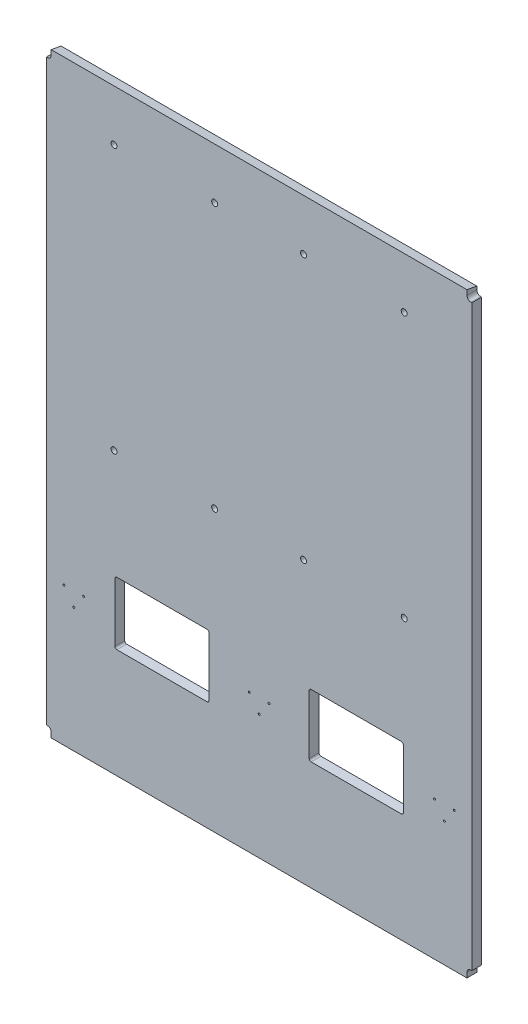
SolidWorks part; units mm, degrees
ref_plane "Front Plane" through (0, 0, 0) normal (0, 0, 1) x (1, 0, 0)
ref_plane "Top Plane" through (0, 0, 0) normal (0, 1, 0) x (1, 0, 0)
ref_plane "Right Plane" through (0, 0, 0) normal (1, 0, 0) x (0, 0, -1)
sketch "Sketch1" plane through (0, 0, 0) normal (0, 0, 1) x (1, 0, 0)
  line L1 (336.55, 482.6) -> (-336.55, 482.6)
  line L2 (336.55, 482.6) -> (336.55, -482.6)
  line L3 (336.55, -482.6) -> (-336.55, -482.6)
  line L4 (-336.55, 482.6) -> (-336.55, -482.6)
  line L5 (336.55, 482.6) -> (-336.55, -482.6) construction
  line L6 (336.55, -482.6) -> (-336.55, 482.6) construction
  point P0 (0, 0)
  dimension "D1" = 673.1
  dimension "D2" = 965.2
extrude "Boss-Extrude1" add sketch "Sketch1" along normal mid plane 15.875
sketch "Sketch2" plane through (0, 0, 7.9375) normal (0, 0, 1) x (1, 0, 0)
  line L0 (0, 0) -> (0, -482.6) construction
  line L1 (-336.55, -482.6) -> (336.55, -482.6) construction
  line L2 (-336.55, 482.6) -> (-336.55, -482.6) construction
  line L3 (-230.3281, -204.0862) -> (-84.2781, -204.0862)
  line L4 (-233.5031, -207.2612) -> (-233.5031, -302.5112)
  line L5 (-230.3281, -305.6862) -> (-84.2781, -305.6862)
  line L6 (-81.1031, -207.2612) -> (-81.1031, -302.5112)
  line L7 (-336.55, -482.6) -> (336.55, -482.6) construction
  line L8 (81.1031, -207.2612) -> (81.1031, -302.5112)
  line L9 (230.3281, -305.6862) -> (84.2781, -305.6862)
  line L10 (233.5031, -207.2612) -> (233.5031, -302.5112)
  line L11 (230.3281, -204.0862) -> (84.2781, -204.0862)
  arc A1 (-84.2781, -204.0862) -> (-81.1031, -207.2612) centre (-84.2781, -207.2612) cw
  arc A2 (-84.2781, -305.6862) -> (-81.1031, -302.5112) centre (-84.2781, -302.5112) ccw
  arc A3 (-233.5031, -302.5112) -> (-230.3281, -305.6862) centre (-230.3281, -302.5112) ccw
  arc A4 (-230.3281, -204.0862) -> (-233.5031, -207.2612) centre (-230.3281, -207.2612) ccw
  arc A5 (230.3281, -204.0862) -> (233.5031, -207.2612) centre (230.3281, -207.2612) cw
  arc A6 (233.5031, -302.5112) -> (230.3281, -305.6862) centre (230.3281, -302.5112) cw
  arc A7 (84.2781, -305.6862) -> (81.1031, -302.5112) centre (84.2781, -302.5112) cw
  arc A8 (84.2781, -204.0862) -> (81.1031, -207.2612) centre (84.2781, -207.2612) ccw
  point P6 (-81.1031, -204.0862)
  point P11 (-233.5031, -305.6862)
  point P14 (-233.5031, -204.0862)
  dimension "D1" = 101.6
  dimension "D3" = 3.175
  dimension "D2" = 152.4
  dimension "D4" = 103.0469
  dimension "D5" = 176.9138
extrude "Cut-Extrude1" cut sketch "Sketch2" against normal through all both and the other way through all
sketch "Sketch3" plane through (336.55, 0, 0) normal (1, 0, 0) x (0, 0, -1)
  line L0 (-7.9375, 482.6) -> (7.9375, 479.8008)
  line L1 (7.9375, -482.6) -> (7.9375, 482.6) construction
  line L2 (7.9375, 479.8008) -> (7.9375, 482.6)
  line L3 (7.9375, 482.6) -> (-7.9375, 482.6)
  dimension "D1" = 10
extrude "Cut-Extrude2" cut sketch "Sketch3" against normal through all
sketch "Sketch4" plane through (0, 0, 7.9375) normal (0, 0, 1) x (1, 0, 0)
  line L0 (-336.55, 482.6) -> (-336.55, -482.6) construction
  line L1 (-336.55, 468.3125) -> (-344.4875, 468.3125)
  line L2 (-336.55, 468.3125) -> (-336.55, -468.3125)
  line L3 (-336.55, -468.3125) -> (-344.4875, -468.3125)
  line L4 (-344.4875, 468.3125) -> (-344.4875, -468.3125)
  line L5 (336.55, -482.6) -> (336.55, 482.6) construction
  line L6 (336.55, 468.3125) -> (344.4875, 468.3125)
  line L7 (336.55, 468.3125) -> (336.55, -468.3125)
  line L8 (336.55, -468.3125) -> (344.4875, -468.3125)
  line L9 (344.4875, 468.3125) -> (344.4875, -468.3125)
  line L10 (0, 0) -> (0, 87.9986) construction
  line L12 (0, 0) -> (-174.9175, 0) construction
  line L13 (-336.55, -482.6) -> (336.55, -482.6) construction
  dimension "D1" = 14.2875
  dimension "D2" = 7.9375
  dimension "D3" = 688.975
extrude "Boss-Extrude2" add sketch "Sketch4" against normal up to surface (15.875 mm away) up to face at (0, -1.3996, -7.9375)
fillet "Fillet1" radius 6.35 4 edges at (336.55, -468.3125, 0) (-336.55, -468.3125, 0) (-336.55, 468.3125, 0) (336.55, 468.3125, 0)
sketch "Sketch5" plane through (0, 0, 7.9375) normal (0, 0, 1) x (1, 0, 0)
  line L0 (-301.5961, -297.8717) -> (-145.6989, -297.8717) construction
  line L1 (-300, -280.8717) -> (-300, -246.7738) construction
  line L2 (0, 0) -> (0, -280.8717) construction
  line L3 (-300, -309.3289) -> (-300, -255.3083) construction
  line L4 (-336.55, -482.6) -> (336.55, -482.6) construction
  circle A0 centre (-316, -257.8717) radius 1.5875
  circle A1 centre (-284, -257.8717) radius 1.5875
  circle A2 centre (-300, -280.8717) radius 1.5875
  circle A6 centre (-16, -257.8717) radius 1.5875
  circle A7 centre (16, -257.8717) radius 1.5875
  circle A8 centre (0, -280.8717) radius 1.5875
  circle A9 centre (284, -257.8717) radius 1.5875
  circle A10 centre (300, -280.8717) radius 1.5875
  circle A11 centre (316, -257.8717) radius 1.5875
  dimension "D1" = 3.175
  dimension "D2" = 17
  dimension "D3" = 23
  dimension "D4" = 32
  dimension "D5" = 32
  dimension "D6" = 201.7283
  dimension "D7" = 300
extrude "Cut-Extrude3" cut sketch "Sketch5" against normal blind 8
sketch "Sketch6" plane through (0, 0, -7.9375) normal (0, 0, -1) x (-1, 0, 0)
  line L0 (0, 0) -> (0, 482.6) construction
  circle A0 centre (-234.95, 400.05) radius 4.826
  circle A1 centre (-71.9667, 400.05) radius 4.826
  circle A2 centre (71.9667, 400.05) radius 4.826
  circle A3 centre (234.95, 400.05) radius 4.826
  circle A4 centre (-234.95, -28.575) radius 4.826
  circle A5 centre (-71.9667, -28.575) radius 4.826
  circle A6 centre (71.9667, -28.575) radius 4.826
  circle A7 centre (234.95, -28.575) radius 4.826
  dimension "D1" = 469.9
  dimension "D2" = 143.9333
  dimension "D3" = 28.575
  dimension "D4" = 9.652
  dimension "D5" = 428.625
extrude "Cut-Extrude4" cut sketch "Sketch6" against normal through all
